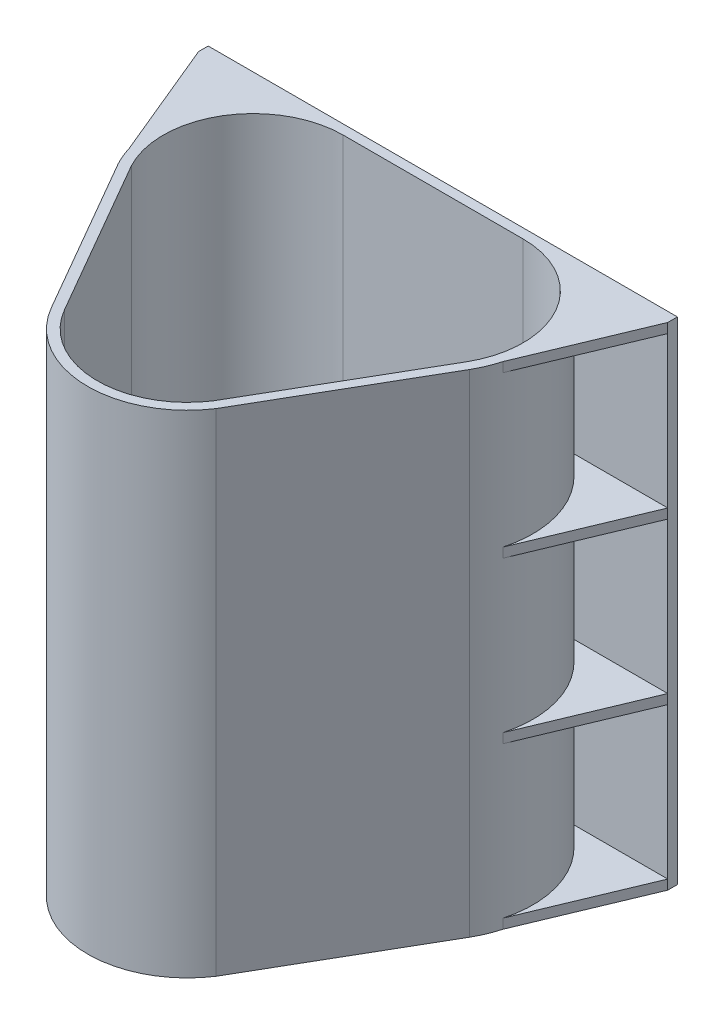
SolidWorks part; units mm, degrees
ref_plane "前视基准面" through (0, 0, 0) normal (0, 0, 1) x (1, 0, 0)
ref_plane "上视基准面" through (0, 0, 0) normal (0, 1, 0) x (1, 0, 0)
ref_plane "右视基准面" through (0, 0, 0) normal (1, 0, 0) x (0, 0, -1)
sketch "草图1" plane through (0, 0, 0) normal (0, 1, 0) x (1, 0, 0)
  line L0 (-12.1261, -31.5457) -> (-26.3407, -6.9111)
  line L3 (11.6971, -32.2414) -> (26.1186, -7.31)
  line L4 (14, 13.7) -> (-14, 13.7)
  line L5 (0, 13.7) -> (0, -44.5594) construction
  arc A3 (26.1186, -7.31) -> (14, 13.7) centre (14, -0.3) ccw
  arc A5 (-12.1261, -31.5457) -> (11.6971, -32.2414) centre (0, -24.5487) ccw
  arc A6 (-14, 13.7) -> (-26.3407, -6.9111) centre (-14, -0.3) ccw
  point P1 (0, 0)
  dimension "D1" = 14
  dimension "D2" = 14
  dimension "D7" = 14
  dimension "D3" = 28
  dimension "D4" = 28
  dimension "D6" = 28
extrude "凸台-拉伸1" add sketch "草图1" along normal blind 75
shell "抽壳1" thickness 1.5 removed face at (-0.1031, 75, 8.3767) outward yes
sketch "草图2" plane through (0, -1.5, 0) normal (0, -1, 0) x (1, 0, 0)
  line L6 (-4.7638, 27.2975) -> (-18.8961, 2.8057)
  line L7 (-14, -5.2) -> (14, -5.2)
  line L8 (18.7609, 3.0539) -> (4.4894, 27.726)
  line L9 (-4.7638, 27.2975) -> (-18.8961, 2.8057)
  line L10 (-14, -5.2) -> (14, -5.2)
  line L11 (18.7609, 3.0539) -> (4.4894, 27.726)
  arc A6 (4.4894, 27.726) -> (-4.7638, 27.2975) centre (0, 24.5487) ccw
  arc A7 (-18.8961, 2.8057) -> (-14, -5.2) centre (-14, 0.3) ccw
  arc A8 (14, -5.2) -> (18.7609, 3.0539) centre (14, 0.3) ccw
  arc A9 (4.4894, 27.726) -> (-4.7638, 27.2975) centre (0, 24.5487) ccw
  arc A10 (-18.8961, 2.8057) -> (-14, -5.2) centre (-14, 0.3) ccw
  arc A11 (14, -5.2) -> (18.7609, 3.0539) centre (14, 0.3) ccw
  dimension "D1" = 10
extrude "切除-拉伸1" cut sketch "草图2" against normal blind 10
sketch "草图5" plane through (0, 0, -15.2) normal (0, 0, -1) x (-1, 0, 0)
  line L2 (-36.5, -1.5) -> (-36.5, 75)
  line L3 (-36.5, 75) -> (36.5, 75)
  line L4 (36.5, -1.5) -> (36.5, 75)
  line L5 (29.5, 75) -> (14, 75) construction
  line L6 (0, -1.5) -> (0, 82.4851) construction
  line L7 (-14, -1.5) -> (14, -1.5) construction
  line L8 (-36.5, -1.5) -> (36.5, -1.5)
  line L9 (-29.5, 75) -> (-29.5, -1.5) construction
  dimension "D1" = 7
extrude "凸台-拉伸2" add sketch "草图5" against normal blind 1.5
ref_plane "基准面1" through (-26.2984, 0, 10.9041) normal (0.9237, 0, -0.383) x (-0.383, 0, -0.9237)
sketch "草图9" plane through (-26.2984, 0, 10.9041) normal (0.9237, 0, -0.383) x (-0.383, 0, -0.9237)
  line L0 (3.5327, 75) -> (3.5327, -1.5) construction
  line L1 (26.6352, 75) -> (3.5327, 75)
  line L2 (26.6352, 75) -> (26.6352, 73.5)
  line L3 (26.6352, 73.5) -> (3.5327, 73.5)
  line L4 (3.5327, 75) -> (3.5327, 73.5)
  dimension "D1" = 1.5
extrude "凸台-拉伸3" add sketch "草图9" along normal up to next
pattern_linear "阵列(线性)1" count 4 spacing 25 along (0, -1, 0) of "凸台-拉伸3"
ref_plane "基准面2" through (26.2146, 0, 10.9419) normal (0.9228, 0, 0.3852) x (0.3852, 0, -0.9228)
sketch "草图10" plane through (26.2146, 0, 10.9419) normal (0.9228, 0, 0.3852) x (0.3852, 0, -0.9228)
  line L0 (3.1217, 75) -> (3.1217, -1.5) construction
  line L1 (26.7023, 75) -> (3.1217, 75)
  line L2 (26.7023, 75) -> (26.7023, 73.5)
  line L3 (26.7023, 73.5) -> (3.1217, 73.5)
  line L4 (3.1217, 75) -> (3.1217, 73.5)
  dimension "D1" = 1.5
extrude "凸台-拉伸4" add sketch "草图10" against normal up to next
pattern_linear "阵列(线性)2" count 4 spacing 25 along (0, -1, 0) of "凸台-拉伸4"
